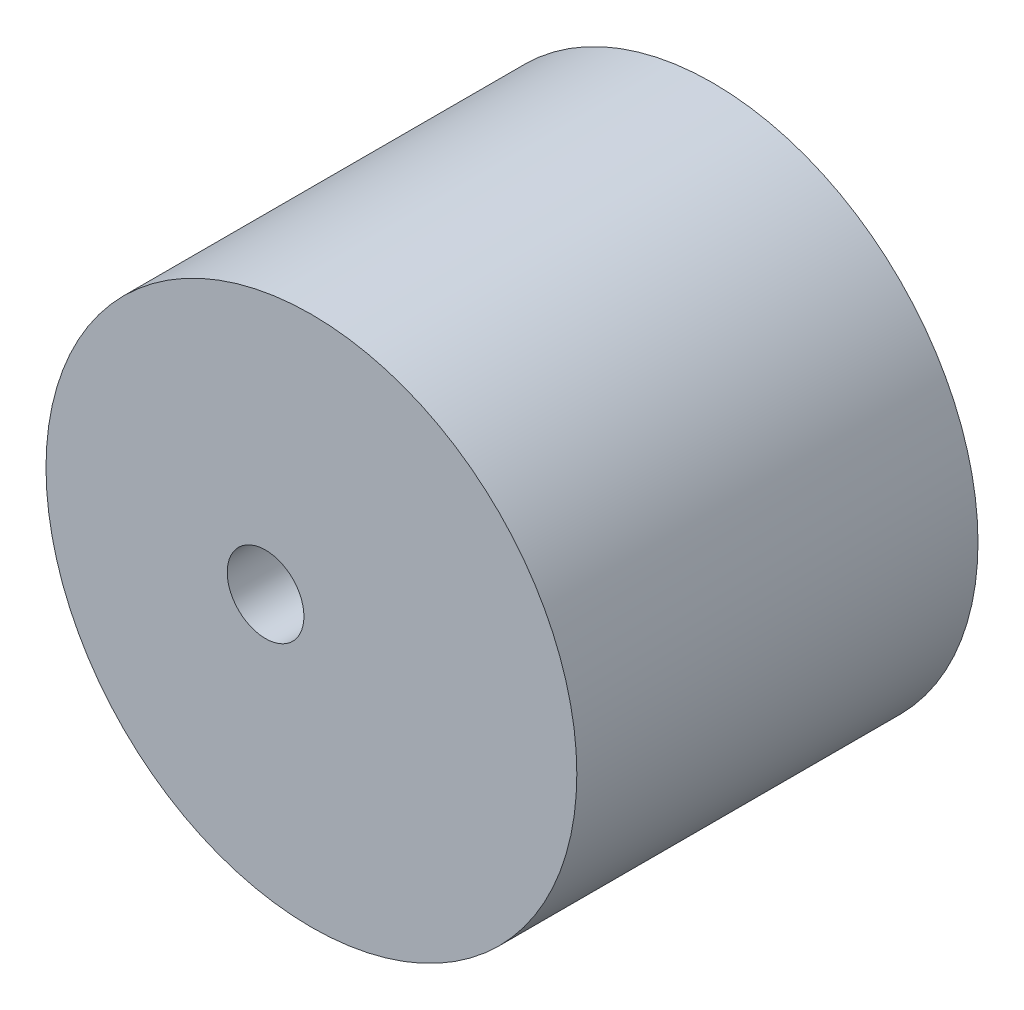
SolidWorks part; units mm, degrees
ref_plane "Front Plane" through (0, 0, 0) normal (0, 0, 1) x (1, 0, 0)
ref_plane "Top Plane" through (0, 0, 0) normal (0, 1, 0) x (1, 0, 0)
ref_plane "Right Plane" through (0, 0, 0) normal (1, 0, 0) x (0, 0, -1)
sketch "Sketch11" plane through (0, 0, 0) normal (0, 0, 1) x (1, 0, 0)
  circle A0 centre (0, 0) radius 23.1562
  circle A1 centre (-4, 0) radius 3.3475
extrude "Boss-Extrude13" add sketch "Sketch11" along normal blind 35
